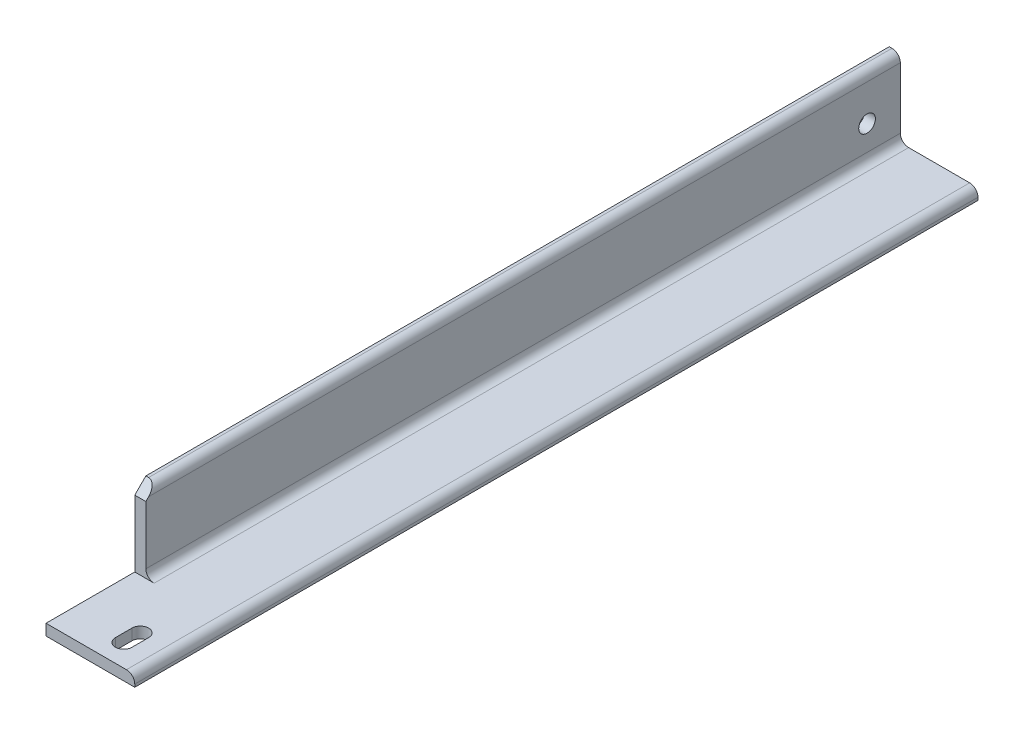
SolidWorks part; units mm, degrees
ref_plane "Front Plane" through (0, 0, 0) normal (0, 0, 1) x (1, 0, 0)
ref_plane "Top Plane" through (0, 0, 0) normal (0, 1, 0) x (1, 0, 0)
ref_plane "Right Plane" through (0, 0, 0) normal (1, 0, 0) x (0, 0, -1)
sketch "Sketch1" plane through (0, 0, 0) normal (0, 0, 1) x (1, 0, 0)
  line L0 (0, 0) -> (0, 101.6)
  line L1 (0, 101.6) -> (3.1801, 101.6)
  line L2 (12.7, 92.0801) -> (12.7, 22.225)
  line L3 (22.225, 12.7) -> (92.0801, 12.7)
  line L4 (101.6, 3.1801) -> (101.6, 0)
  line L5 (101.6, 0) -> (0, 0)
  arc A0 (101.6, 3.1801) -> (92.0801, 12.7) centre (92.0801, 3.1801) ccw
  arc A1 (3.1801, 101.6) -> (12.7, 92.0801) centre (3.1801, 92.0801) cw
  arc A2 (22.225, 12.7) -> (12.7, 22.225) centre (22.225, 22.225) cw
  circle A3 centre (0, 0) radius 9.525 construction
  dimension "D2" = 3.1801
  dimension "Radius_1" = 9.525
  dimension "Radius_2" = 9.525
  dimension "D1" = 12.7
  dimension "V_leg" = 101.6
  dimension "H_leg" = 101.6
  dimension "Thickness" = 12.7
  dimension "Flat_wid" = 3.1801
extrude "Boss-Extrude1" add sketch "Sketch1" along normal mid plane 965.2
sketch "Sketch2" plane through (0, 0, 0) normal (1, 0, 0) x (0, 1, 0)
  line L0 (101.6, 482.6) -> (101.6, -482.6) construction
  line L1 (12.7, 482.6) -> (12.7, 381)
  line L2 (12.7, 381) -> (88.9, 381)
  line L3 (101.6, 482.6) -> (0, 482.6) construction
  line L4 (12.7, 482.6) -> (101.6, 482.6)
  line L5 (101.6, 482.6) -> (101.6, 381)
  line L6 (0, 482.6) -> (0, -482.6) construction
  line L7 (88.9, 381) -> (101.6, 368.3)
  line L8 (101.6, 368.3) -> (101.6, 381)
  dimension "D1" = 12.7
  dimension "D2" = 12.7
  dimension "D3" = 101.6
  dimension "D4" = 12.7
sketch "Sketch3" plane through (0, 0, 0) normal (0, 1, 0) x (0, 0, 1)
  line L0 (457.2, 63.5) -> (438.15, 63.5) construction
  line L1 (457.2, 53.975) -> (438.15, 53.975)
  line L2 (457.2, 73.025) -> (438.15, 73.025)
  line L5 (482.6, 0) -> (482.6, 101.6) construction
  arc A0 (457.2, 53.975) -> (457.2, 73.025) centre (457.2, 63.5) ccw
  arc A1 (438.15, 73.025) -> (438.15, 53.975) centre (438.15, 63.5) ccw
  point P2 (447.675, 63.5)
  dimension "D1" = 9.525
  dimension "D2" = 38.1
  dimension "D3" = 19.05
  dimension "D4" = 25.4
extrude "Cut-Extrude4" cut sketch "Sketch2" along normal up to next
extrude "Cut-Extrude2" cut sketch "Sketch3" along normal up to next
hole_wizard "3/4 (0.75) Diameter Hole2" positions "Sketch7" profile "Sketch6" hole size "3/4" standard "Ansi Inch" end condition up to next
sketch "Sketch7" plane through (0, 0, 0) normal (-1, 0, 0) x (0, 0, 1)
  line L0 (482.6, 0) -> (-482.6, 0) construction
  line L1 (-482.6, 101.6) -> (-482.6, 0) construction
  point P0 (-444.5, 50.8)
  dimension "D1" = 50.8
  dimension "D2" = 38.1
sketch "Sketch6" plane through (0, 50.8, -444.5) normal (0, 1, 0) x (0, 0, 1)
  line L0 (0, 0) -> (0, 12.7)
  line L1 (0, 12.7) -> (9.525, 12.7)
  line L2 (9.525, 12.7) -> (9.525, 0)
  line L5 (9.525, 0) -> (0, 0)
  line L11 (0, -6.35) -> (0, 107.95) construction
  dimension "Thru Hole Dia." = 19.05
  dimension "Thru Hole Depth" = 12.7
